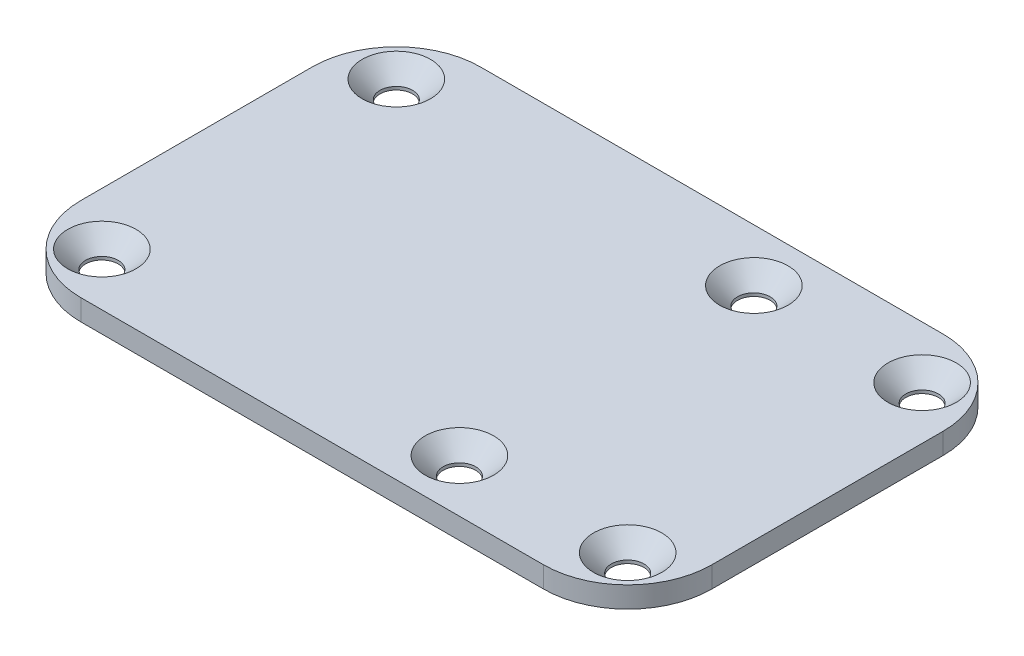
SolidWorks part; units mm, degrees
material "6063-T6"
ref_plane "Front Plane" through (0, 0, 0) normal (0, 0, 1) x (1, 0, 0)
ref_plane "Top Plane" through (0, 0, 0) normal (0, 1, 0) x (1, 0, 0)
ref_plane "Right Plane" through (0, 0, 0) normal (1, 0, 0) x (0, 0, -1)
sketch "Sketch1" plane through (0, 0, 0) normal (0, 1, 0) x (1, 0, 0)
  line L1 (22, -19) -> (-22, -19)
  line L2 (30, -11) -> (30, 11)
  line L3 (22, 19) -> (-22, 19)
  line L4 (-30, -11) -> (-30, 11)
  line L5 (30, -19) -> (-30, 19) construction
  line L6 (30, 19) -> (-30, -19) construction
  arc A0 (30, 11) -> (22, 19) centre (22, 11) ccw
  arc A1 (22, -19) -> (30, -11) centre (22, -11) ccw
  arc A2 (-22, -19) -> (-30, -11) centre (-22, -11) cw
  arc A3 (-22, 19) -> (-30, 11) centre (-22, 11) ccw
  point P0 (0, 0)
  dimension "D3" = 8
  dimension "D1" = 60
  dimension "D2" = 38
extrude "Boss-Extrude1" add sketch "Sketch1" along normal blind 2
hole_wizard "Ø3.1 (3.1) Diameter Hole1" positions "Location" profile "Hole" hole size "Ø3.1" standard "ANSI Metric" end condition through all
sketch "Location" plane through (0, 2, 0) normal (0, -1, 0) x (-1, 0, 0)
  line L4 (-33.1926, 0) -> (33.4931, 0) construction
  line L6 (0, 17.9223) -> (0, -17.6691) construction
  point P0 (-25, 14)
  point P2 (-25, -14)
  point P4 (25, -14)
  point P6 (25, 14)
  point P29 (-9, 14)
  point P31 (-9, -14)
  point P42 (0, 0)
  point P43 (0, 0)
  point P44 (0, 0)
  point P45 (0, 0)
  point P46 (-6.1164, -14)
  point P47 (-4.1738, 14)
  point P48 (0, 0)
  point P49 (-5.7764, 14)
  dimension "D1" = 28
  dimension "D2" = 25
  dimension "D3" = 25
  dimension "D4" = 16
sketch "Hole" plane through (25, 2, -14) normal (1, 0, 0) x (0, 0, 1)
  line L0 (0, 0) -> (0, 2)
  line L1 (0, 2) -> (1.55, 2)
  line L2 (1.55, 2) -> (1.55, 1.7)
  line L3 (1.55, 1.7) -> (3.25, 0)
  line L5 (3.25, 0) -> (0, 0)
  line L6 (-1.55, 1.7) -> (-3.25, 0) construction
  line L11 (0, -6.35) -> (0, 107.95) construction
  dimension "Thru Hole Dia." = 3.1
  dimension "Thru Hole Depth" = 2
  dimension "Near C'Sink Dia." = 6.5
  dimension "Near C'Sink Angle" = 90
